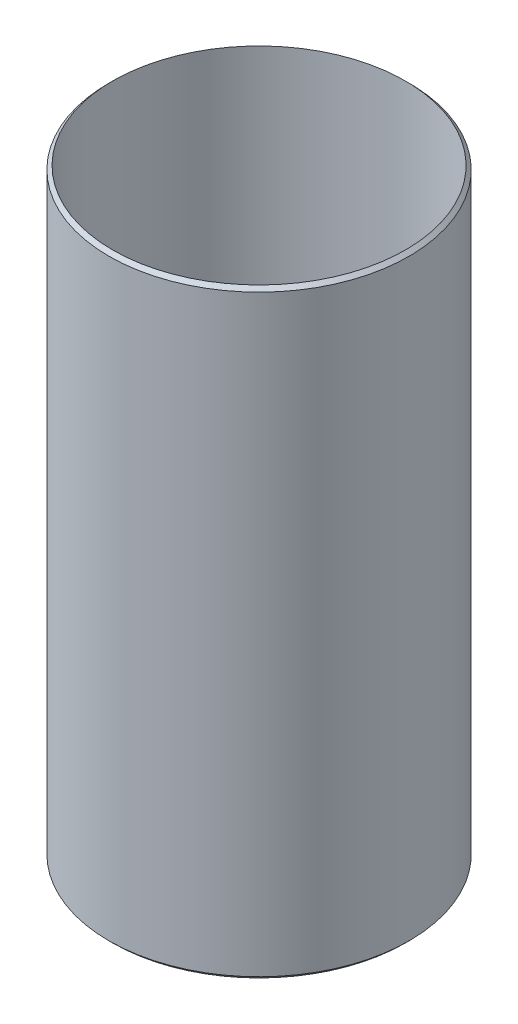
SolidWorks part; units mm, degrees
material "6061-T6 (SS)"
ref_plane "Front Plane" through (0, 0, 0) normal (0, 0, 1) x (1, 0, 0)
ref_plane "Top Plane" through (0, 0, 0) normal (0, 1, 0) x (1, 0, 0)
ref_plane "Right Plane" through (0, 0, 0) normal (1, 0, 0) x (0, 0, -1)
sketch "Sketch1" plane through (0, 0, 0) normal (0, 1, 0) x (1, 0, 0)
  circle A0 centre (0, 0) radius 76.55
  circle A1 centre (0, 0) radius 82.55
  dimension "D1" = 165.1
  dimension "D2" = 6
extrude "Boss-Extrude1" add sketch "Sketch1" along normal blind 330.2
chamfer "Chamfer1" distance 2 angle 45 2 edges at (0, 0, 82.55) (0, 330.2, 82.55)
sketch "Sketch2" plane through (0, 0, 0) normal (0, -1, 0) x (1, 0, 0)
  circle A0 centre (0, 0) radius 80.55
  dimension "D1" = 161.1
extrude "Cut-Extrude1" cut sketch "Sketch2" against normal blind 165.1
sketch "Sketch3" plane through (0, 330.2, 0) normal (0, 1, 0) x (1, 0, 0)
  circle A0 centre (0, 0) radius 80.55
  dimension "D1" = 161.1
extrude "Cut-Extrude2" cut sketch "Sketch3" against normal blind 117.95
equation "\"TubeDiameter\"= 6.500in"
equation "\"D1@Sketch1\"=\"TubeDiameter\""
